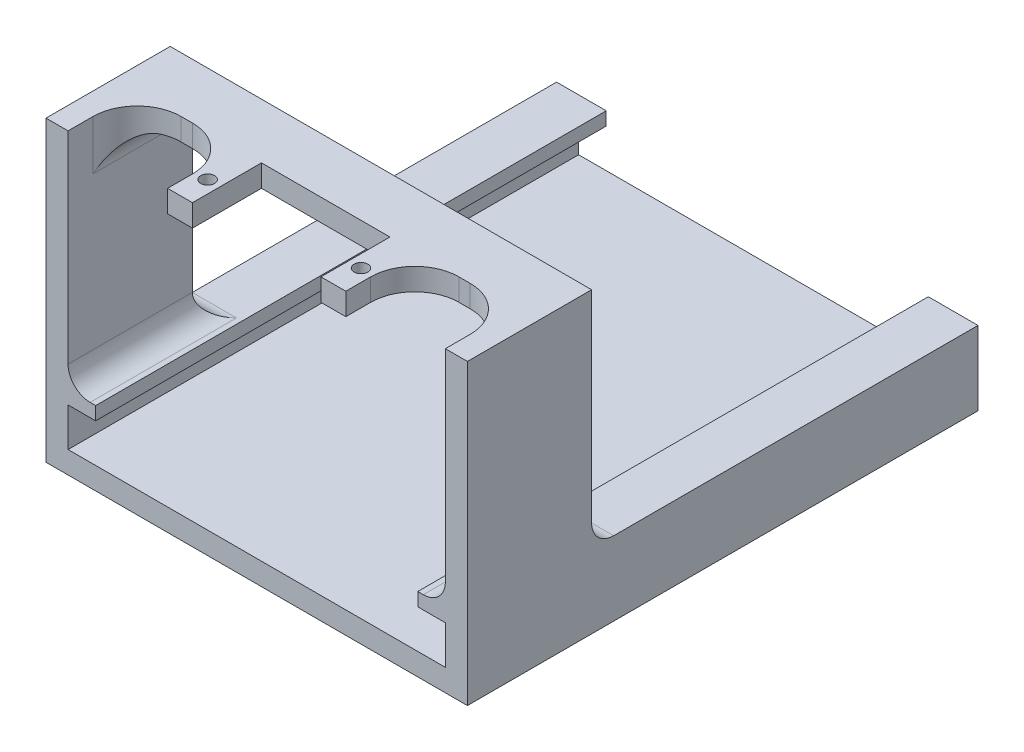
SolidWorks part; units mm, degrees
ref_plane "Спереди" through (0, 0, 0) normal (0, 0, 1) x (1, 0, 0)
ref_plane "Сверху" through (0, 0, 0) normal (0, 1, 0) x (1, 0, 0)
ref_plane "Справа" through (0, 0, 0) normal (1, 0, 0) x (0, 0, -1)
sketch "Эскиз1" plane through (0, 0, 0) normal (0, 0, 1) x (1, 0, 0)
  line L0 (38.175, 4) -> (38.175, 0) construction
  line L1 (0, 0) -> (76.35, 0)
  line L2 (0, 0) -> (0, 4)
  line L3 (0, 4) -> (76.35, 4)
  line L4 (76.35, 0) -> (76.35, 4)
  line L5 (0, 0) -> (4, 0)
  line L26 (72.35, 0) -> (72.35, -36.6)
  line L27 (76.35, 0) -> (72.35, 0)
  line L28 (76.35, 0) -> (76.35, -50)
  line L29 (76.35, -50) -> (0, -50)
  line L30 (72.35, 0) -> (76.35, 0)
  line L33 (76.35, 0) -> (76.35, -50)
  line L34 (38.175, -50) -> (38.175, -46)
  line L36 (4, -46) -> (72.35, -46)
  line L37 (72.35, -46) -> (72.35, -39)
  line L38 (72.35, -39) -> (67.35, -39)
  line L39 (67.35, -39) -> (67.35, -36.6)
  line L40 (67.35, -36.6) -> (72.35, -36.6)
  line L41 (4, -46) -> (4, -39)
  line L42 (4, -39) -> (9, -39)
  line L43 (9, -39) -> (9, -36.6)
  line L44 (9, -36.6) -> (4, -36.6)
  line L45 (4, 0) -> (4, -36.6)
  line L46 (0, 0) -> (0, -50)
  line L49 (0, -37) -> (0, -50)
  line L50 (76.35, -37) -> (76.35, -50)
  dimension "D1" = 50
  dimension "D2" = 2.4
  dimension "D3" = 7
  dimension "D4" = 4
  dimension "D5" = 5
  dimension "D6" = 68.35
  dimension "D8" = 4
extrude "Бобышка-Вытянуть7" add sketch "Эскиз1" along normal blind 5 and the other way blind 5 contours L40 L39 L38 L37 L36 L34 L29 L33 L28 L1 L26 | L1 L46 L29 L34 L36 L41 L42 L43 L44 L45 | L3 L0 L1 L4 | L0 L3 L2 L1 region at (57.2625, 2, 0) region at (19.0875, 2, 0) region at (3.3709, -18.3, 0) region at (74.35, -0.6291, 0)
sketch "Эскиз2" plane through (0, 0, 5) normal (0, 0, 1) x (1, 0, 0)
  line L0 (4, -39) -> (9, -39)
  line L1 (9, -39) -> (9, -36.6)
  line L2 (9, -39) -> (9, -36.6) construction
  line L3 (9, -36.6) -> (4, -36.6)
  line L4 (4, -36.6) -> (0, -36.6)
  line L5 (0, 4) -> (0, -50) construction
  line L6 (0, -36.6) -> (0, -50)
  line L7 (0, -50) -> (76.35, -50)
  line L8 (76.35, -50) -> (76.35, -36.6)
  line L9 (76.35, 4) -> (76.35, -50) construction
  line L10 (76.35, -36.6) -> (67.35, -36.6)
  line L11 (67.35, -36.6) -> (67.35, -39)
  line L12 (67.35, -39) -> (72.35, -39)
  line L13 (72.35, -39) -> (72.35, -46)
  line L14 (4, -46) -> (72.35, -46) construction
  line L15 (72.35, -46) -> (72.35, -39) construction
  line L16 (72.35, -46) -> (4, -46)
  line L29 (4, 0) -> (4, -36.6)
  line L30 (72.35, 0) -> (4, 0)
  line L31 (72.35, -36.6) -> (72.35, 0)
  line L32 (67.35, -36.6) -> (72.35, -36.6)
  line L33 (67.35, -39) -> (67.35, -36.6)
  line L34 (72.35, -39) -> (67.35, -39)
  line L35 (72.35, -46) -> (72.35, -39)
  line L36 (4, -46) -> (72.35, -46)
  line L37 (4, -39) -> (4, -46)
  line L38 (9, -39) -> (4, -39)
  line L39 (9, -36.6) -> (9, -39)
  line L40 (4, -36.6) -> (9, -36.6)
  line L41 (4, 0) -> (4, -36.6)
  line L42 (72.35, 0) -> (4, 0)
  line L43 (72.35, -36.6) -> (72.35, 0)
  line L44 (67.35, -36.6) -> (72.35, -36.6)
  line L45 (67.35, -39) -> (67.35, -36.6)
  line L46 (72.35, -39) -> (67.35, -39)
  line L47 (72.35, -46) -> (72.35, -39)
  line L48 (4, -46) -> (72.35, -46)
  line L50 (9, -39) -> (4, -39)
  line L51 (9, -36.6) -> (9, -39)
  line L52 (4, -36.6) -> (9, -36.6)
  line M16 (72.35, -36.6) -> (67.35, -36.6)
  line M17 (67.35, -36.6) -> (67.35, -39)
  line M18 (67.35, -39) -> (72.35, -39)
  line M19 (72.35, -39) -> (72.35, -46)
  line M20 (72.35, -46) -> (4, -46)
  line M21 (4, -46) -> (4, -39)
  line M22 (4, -39) -> (9, -39)
  line M23 (9, -39) -> (9, -36.6)
  line M24 (9, -36.6) -> (4, -36.6)
  line M26 (0, 4) -> (0, -50)
  line M27 (0, -50) -> (76.35, -50)
  line M28 (76.35, -50) -> (76.35, 4)
  dimension "D1" = 0
extrude "Бобышка-Вытянуть8" add sketch "Эскиз2" against normal blind 80 and the other way blind 12.5 contours L10 L4 M28 M16 M17 M18 M19 M20 M21 M22 M23 M24 M26 M27 region at (38.175, -46.1497, 5)
sketch "Эскиз3" plane through (0, 0, 5) normal (0, 0, 1) x (1, 0, 0)
  line L0 (38.175, 4) -> (38.175, 0) construction
  line L1 (0, 4) -> (76.35, 4) construction
  line L2 (4, 0) -> (72.35, 0) construction
  line L3 (54.315, 0) -> (49.815, 0)
  line L4 (22.035, 4) -> (26.535, 4)
  line L6 (22.035, 0) -> (26.535, 0)
  line L7 (26.535, 4) -> (26.535, 0)
  line L8 (54.315, 4) -> (49.815, 4)
  line L10 (49.815, 4) -> (49.815, 0)
  line L11 (22.035, 4) -> (22.035, 0)
  line L12 (54.315, 4) -> (54.315, 0)
  line L15 (0, 4) -> (4, 4)
  line L16 (0, 4) -> (0, -36.6)
  line L17 (0, -36.6) -> (4, -36.6)
  line L18 (4, 4) -> (4, -36.6)
  line L19 (76.35, 4) -> (72.35, 4)
  line L20 (76.35, 4) -> (76.35, -36.6)
  line L21 (76.35, -36.6) -> (72.35, -36.6)
  line L22 (72.35, 4) -> (72.35, -36.6)
  dimension "D1" = 23.28
  dimension "D2" = 4.5
extrude "Бобышка-Вытянуть9" add sketch "Эскиз3" along direction (0, 0, 1) on the side of the normal blind 12.5
sketch "Эскиз5" plane through (0, 4, 0) normal (0, 1, 0) x (1, 0, 0)
  line L0 (38.175, -5) -> (38.175, 5) construction
  line L1 (26.535, -5) -> (49.815, -5) construction
  line L2 (0, 5) -> (76.35, 5) construction
  line L3 (24.285, -17.5) -> (24.285, 5) construction
  line L4 (26.535, -17.5) -> (22.035, -17.5) construction
  line L5 (52.065, -17.5) -> (52.065, 5) construction
  line L6 (54.315, -17.5) -> (49.815, -17.5) construction
  line L7 (24.285, -12.5) -> (52.065, -12.5) construction
  circle A0 centre (24.285, -12.5) radius 1.25
  circle A1 centre (52.065, -12.5) radius 1.25
  point P14 (24.285, -12.5)
  dimension "D1" = 5
extrude "Вырез-Вытянуть1" cut sketch "Эскиз5" against normal blind 12.5
fillet "Скругление1" radius 4 1 edges at (2, -36.6, -5) type face fillet first side face at (38.175, -17.3, -5) second side face at (4.3333, -36.6, -20.8333)
fillet "Скругление2" radius 4 1 edges at (74.35, -36.6, -5) type face fillet first side face at (72.0167, -36.6, -20.8333) second side face at (38.175, -16.3, -5)
fillet "Скругление3" radius 8 1 edges at (4, 2, 5) type face fillet first side face at (13.0175, 2, 5) second side face at (4, -14.0898, 3.8326)
fillet "Скругление4" radius 8 1 edges at (72.35, 2, 5) type face fillet first side face at (63.3325, 2, 5) second side face at (72.35, -14.0898, 3.8326)
fillet "Скругление5" radius 8 1 edges at (22.035, 2, 5) type face fillet first side face at (17.0175, 2, 5) second side face at (22.035, 2, 11.25)
fillet "Скругление6" radius 8 1 edges at (54.315, 2, 5) type face fillet first side face at (59.3325, 2, 5) second side face at (54.315, 2, 11.25)
fillet "Скругление7" radius 5 1 edges at (72.35, 0, 4) type face fillet first side face at (72.35, -14.0898, 6.1183) second side face at (25.535, 0, 12.5)
fillet "Скругление8" radius 5 1 edges at (4, 0, 4) type face fillet first side face at (4, -14.0898, 6.1183) second side face at (25.535, 0, 12.5)
fillet "Скругление9" radius 4 1 edges at (4, -36.6, 4.25) type face fillet first side face at (4.3333, -36.6, -22.1667) second side face at (4, -15.5183, 6.1183)
fillet "Скругление10" radius 4 1 edges at (72.35, -36.6, 4.25) type face fillet first side face at (72.0167, -36.6, -22.1667) second side face at (72.35, -15.5183, 6.1183)
